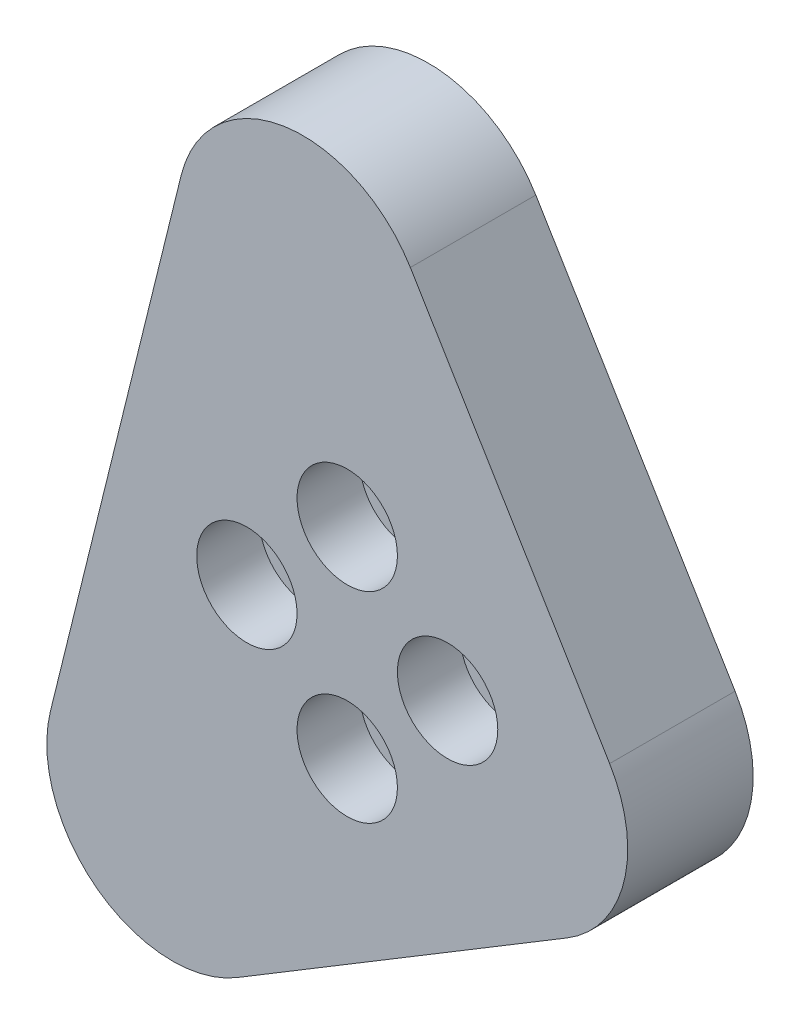
SolidWorks part; units mm, degrees
ref_plane "Front Plane" through (0, 0, 0) normal (0, 0, 1) x (1, 0, 0)
ref_plane "Top Plane" through (0, 0, 0) normal (0, 1, 0) x (1, 0, 0)
ref_plane "Right Plane" through (0, 0, 0) normal (1, 0, 0) x (0, 0, -1)
sketch "Sketch1" plane through (0, 0, 0) normal (0, 0, 1) x (1, 0, 0)
  line L0 (-13.9462, -18.9369) -> (-3.5289, 23.2519) construction
  line L1 (-3.5289, 23.2519) -> (12.3568, -3.0512) construction
  line L2 (12.3568, -3.0512) -> (-13.9462, -18.9369) construction
  line L3 (-23.6546, -16.5397) -> (-13.2373, 25.6491)
  line L4 (5.031, 28.4217) -> (20.9168, 2.1186)
  line L5 (17.5266, -11.6111) -> (-8.7764, -27.4969)
  line L6 (26.0866, -6.4413) -> (-29.442, -39.9779) construction
  line L7 (-29.442, -39.9779) -> (-7.45, 49.0873) construction
  line L8 (-7.45, 49.0873) -> (26.0866, -6.4413) construction
  circle A0 centre (0, 0) radius 9
  arc A3 (-23.6546, -16.5397) -> (-8.7764, -27.4969) centre (-13.9462, -18.9369) ccw
  arc A4 (5.031, 28.4217) -> (-13.2373, 25.6491) centre (-3.5289, 23.2519) ccw
  arc A5 (17.5266, -11.6111) -> (20.9168, 2.1186) centre (12.3568, -3.0512) ccw
  dimension "D1" = 18
  dimension "D2" = 45
  dimension "D3" = 45
  dimension "D4" = 10
extrude "Boss-Extrude1" add sketch "Sketch1" along normal blind 70
sketch "Sketch2" plane through (9.8226, -16.2639, 0) normal (0.517, -0.856, 0) x (0.856, 0.517, 0)
  line L0 (-21.7279, 70) -> (9, 70) construction
  circle A0 centre (0, 65) radius 2.5
  dimension "D1" = 5
  dimension "D2" = 5
extrude "Cut-Extrude1" cut sketch "Sketch2" against normal blind 5
sketch "Sketch3" plane through (7.2377, -11.984, 0) normal (0.517, -0.856, 0) x (0.856, 0.517, 0)
  circle A0 centre (0, 65) radius 1.75
  dimension "D1" = 3.5
extrude "Cut-Extrude2" cut sketch "Sketch3" against normal up to surface (5.1718 mm away) up to face at (9, 0, 70)
pattern_circular "CirPattern1" count 3 over 360 about axis through (0, 0, 0) along (0, 0, 1) of "Cut-Extrude1", "Cut-Extrude2"
sketch "Sketch5" plane through (0, 0, 0) normal (0, 1, 0) x (1, 0, 0)
  line L0 (-24.5682, 0) -> (0, 0) construction
  line L2 (-24.5682, -30) -> (0, -30)
  line L3 (-24.5682, -5) -> (0, -5)
  line L4 (0, 0) -> (0, -30) construction
  line L6 (-24.5682, -30) -> (-24.5682, -5)
  line L7 (0, -30) -> (0, -5)
  dimension "D1" = 5
  dimension "D2" = 25
revolve "Cut-Revolve1" cut sketch "Sketch5" angle 360 about L4
sketch "Sketch6" plane through (0, 0, 0) normal (0, 0, -1) x (-1, 0, 0)
  circle A0 centre (0, 0) radius 9
extrude "Boss-Extrude2" add sketch "Sketch6" against normal up to surface (5 mm away) up to face at (9, 0, 5)
sketch "Sketch8" plane through (0, 0, 30) normal (0, 0, -1) x (-1, 0, 0)
  circle A0 centre (0, 0) radius 9 construction
  circle A1 centre (0, 0) radius 9
  circle A2 centre (0, 0) radius 5.0505
extrude "Boss-Extrude3" add sketch "Sketch8" against normal blind 3
sketch "Sketch9" plane through (0, 0, 0) normal (0, 0, -1) x (-1, 0, 0)
  circle A0 centre (0, 0) radius 8 construction
  circle A1 centre (0, 8) radius 1.875
  circle A2 centre (8, 0) radius 1.875
  circle A3 centre (0, -8) radius 1.875
  circle A4 centre (-8, 0) radius 1.875
  point P14 (0, 0)
  dimension "D1" = 16
  dimension "D2" = 3.75
  dimension "D3" = 4
extrude "Cut-Extrude3" cut sketch "Sketch9" against normal up to surface (5 mm away) up to face at (1.1561, -0.2855, 5)
sketch "Sketch10" plane through (0, 0, 30) normal (0, 0, -1) x (-1, 0, 0)
  line L1 (13.2373, 25.6491) -> (23.6546, -16.5397) construction
  line L2 (8.7764, -27.4969) -> (-17.5266, -11.6111) construction
  line L3 (-20.9168, 2.1186) -> (-5.031, 28.4217) construction
  line L4 (13.2373, 25.6491) -> (23.6546, -16.5397)
  line L5 (8.7764, -27.4969) -> (-17.5266, -11.6111)
  line L6 (-20.9168, 2.1186) -> (-5.031, 28.4217)
  arc A0 (13.2373, 25.6491) -> (-5.031, 28.4217) centre (3.5289, 23.2519) ccw construction
  arc A1 (8.7764, -27.4969) -> (23.6546, -16.5397) centre (13.9462, -18.9369) ccw construction
  arc A2 (-20.9168, 2.1186) -> (-17.5266, -11.6111) centre (-12.3568, -3.0512) ccw construction
  arc A3 (13.2373, 25.6491) -> (-5.031, 28.4217) centre (3.5289, 23.2519) ccw
  arc A4 (8.7764, -27.4969) -> (23.6546, -16.5397) centre (13.9462, -18.9369) ccw
  arc A5 (-20.9168, 2.1186) -> (-17.5266, -11.6111) centre (-12.3568, -3.0512) ccw
sketch "Sketch11" plane through (0, 0, 0) normal (0, 0, -1) x (-1, 0, 0)
  circle A0 centre (0, 0) radius 4
  dimension "D1" = 8
extrude "Cut-Extrude4" cut sketch "Sketch11" against normal blind 3
sketch "Sketch12" plane through (0, 0, 0) normal (1, 0, 0) x (0, 0, -1)
  line L0 (-5, 35.5746) -> (-74.9237, 35.5746)
  line L1 (-74.9237, 35.5746) -> (-74.9237, -36.291)
  line L2 (-74.9237, -36.291) -> (-5, -36.291)
  line L3 (-5, -36.291) -> (-5, 35.5746)
extrude "Cut-Extrude5" cut sketch "Sketch12" against normal through all and the other way through all
sketch "Sketch13" plane through (0, 0, 5) normal (0, 0, 1) x (1, 0, 0)
  line L0 (-8.7764, -27.4969) -> (17.5266, -11.6111) construction
  line L1 (20.9168, 2.1186) -> (5.031, 28.4217) construction
  line L2 (-13.2373, 25.6491) -> (-23.6546, -16.5397) construction
  line L3 (-8.7764, -27.4969) -> (17.5266, -11.6111)
  line L4 (20.9168, 2.1186) -> (5.031, 28.4217)
  line L5 (-13.2373, 25.6491) -> (-23.6546, -16.5397)
  arc A0 (-23.6546, -16.5397) -> (-8.7764, -27.4969) centre (-13.9462, -18.9369) ccw construction
  arc A1 (17.5266, -11.6111) -> (20.9168, 2.1186) centre (12.3568, -3.0512) ccw construction
  arc A2 (5.031, 28.4217) -> (-13.2373, 25.6491) centre (-3.5289, 23.2519) ccw construction
  arc A3 (-23.6546, -16.5397) -> (-8.7764, -27.4969) centre (-13.9462, -18.9369) ccw
  arc A4 (17.5266, -11.6111) -> (20.9168, 2.1186) centre (12.3568, -3.0512) ccw
  arc A5 (5.031, 28.4217) -> (-13.2373, 25.6491) centre (-3.5289, 23.2519) ccw
  circle A6 centre (-8, 0) radius 4
  circle A7 centre (0, 8) radius 4
  circle A8 centre (8, 0) radius 4
  circle A9 centre (0, -8) radius 4
  dimension "D1" = 8
extrude "Boss-Extrude5" add sketch "Sketch13" along normal blind 5
equation "\"fuse_diam\"= 0.07"
equation "\"fuse_rad\"= 0.035"
equation "\"battery_length\"= 0.076"
equation "\"battery_width\"= 0.034"
equation "\"battery_height\"= 0.051"
equation "\"bat_bay_length\"= 0.096"
equation "\"wing_shelf\"= 0.0175"
equation "\"shell\"= 0.002"
equation "\"chord_length\"= 0.089"
equation "\"tail_length\"= 0.26532000000000006"
equation "\"tail_diam\"= 0.035"
equation "\"connector\"= 0.06633000000000001"
